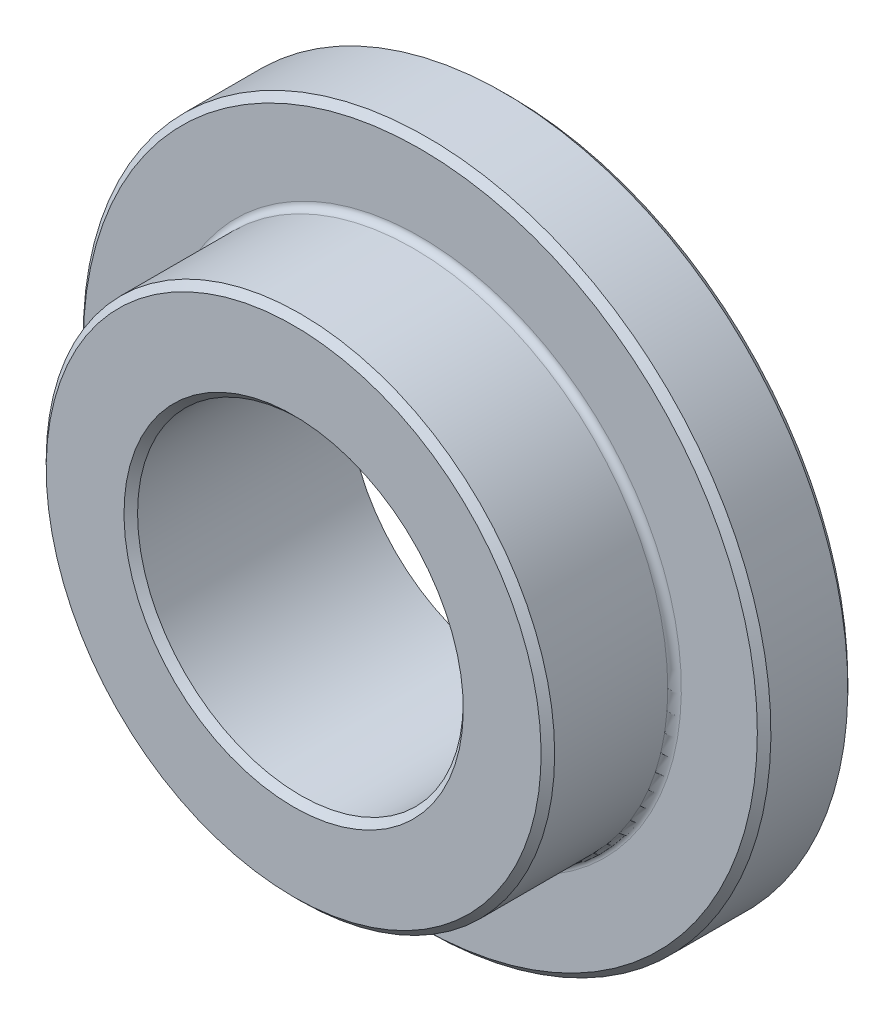
SolidWorks part; units mm, degrees
ref_plane "Front Plane" through (0, 0, 0) normal (0, 0, 1) x (1, 0, 0)
ref_plane "Top Plane" through (0, 0, 0) normal (0, 1, 0) x (1, 0, 0)
ref_plane "Right Plane" through (0, 0, 0) normal (1, 0, 0) x (0, 0, -1)
sketch "Sketch1" plane through (0, 0, 0) normal (0, 0, 1) x (1, 0, 0)
  circle A0 centre (0, 0) radius 4.5
  circle A1 centre (0, 0) radius 7.025
  circle A2 centre (0, 0) radius 9.5
  point P5 (0, 7.025)
  point P6 (0, 4.5)
  point P7 (0, 9.5)
  dimension "ID" = 9
  dimension "OD" = 14.05
  dimension "Flange OD" = 19
sketch "Sketch2" plane through (0, 0, 0) normal (1, 0, 0) x (0, 0, -1)
  line L0 (3, 0) -> (-3, 0)
  line L1 (3, 0) -> (3, 9.5)
  line L2 (3, 9.5) -> (0.5, 9.5)
  line L3 (0.5, 9.5) -> (0.5, 7.025)
  line L4 (0.5, 7.025) -> (-3, 7.025)
  line L5 (-3, 7.025) -> (-3, 4.5)
  line L6 (-3, 4.5) -> (3, 4.5)
  point P4 (0, 0)
  dimension "Flange Thickness" = 2.5
  dimension "Length" = 6
sketch "Sketch3" plane through (0, 0, 0) normal (1, 0, 0) x (0, 0, -1)
  line L0 (3, 9.5) -> (0.5, 9.5) construction
  line L1 (0.5, 9.5) -> (0.5, 7.025) construction
  line L2 (0.5, 7.025) -> (-3, 7.025) construction
  line L3 (-3, 4.5) -> (3, 4.5) construction
  line L4 (-3, 7.025) -> (-3, 4.5) construction
  line L5 (3, 9.5) -> (0.5, 9.5)
  line L6 (0.5, 9.5) -> (0.5, 7.025)
  line L7 (0.5, 7.025) -> (-3, 7.025)
  line L8 (-3, 4.5) -> (3, 4.5)
  line L9 (-3, 7.025) -> (-3, 4.5)
  line L10 (3, 9.5) -> (3, 4.5)
revolve "Revolve1" add sketch "Sketch3" angle 360 about L0
chamfer "Chamfer1" distance 0.1875 angle 45 4 edges at (0, 9.5, -3) (0, 9.5, -0.5) (0, 7.025, 3) (0, 4.5, 3)
fillet "Fillet1" radius 0.1875 1 edges at (0, 7.025, -0.5)
equation "\"D1@Chamfer1\"=\"Flange Thickness@Sketch2\"*.075"
equation "\"D1@Fillet1\"=\"D1@Chamfer1\""
